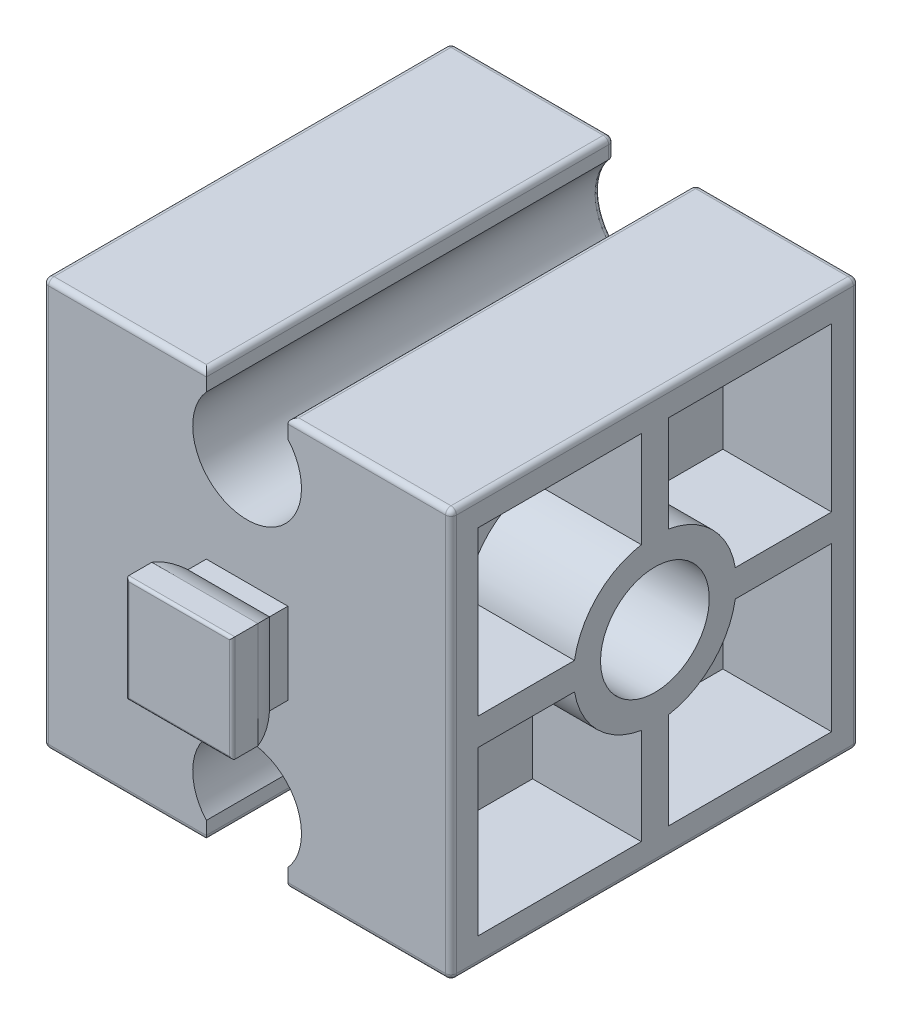
SolidWorks part; units mm, degrees
note: The reader was unsure of these and kept them because the rebuilt part matched: shared geometry of "草图6<2>".
ref_plane "前视基准面" through (0, 0, 0) normal (0, 0, 1) x (1, 0, 0)
ref_plane "上视基准面" through (0, 0, 0) normal (0, 1, 0) x (1, 0, 0)
ref_plane "右视基准面" through (0, 0, 0) normal (1, 0, 0) x (0, 0, -1)
sketch "草图1" plane through (0, 0, 0) normal (0, 0, 1) x (1, 0, 0)
  line L1 (-7.5, -7.5) -> (7.5, -7.5)
  line L2 (-7.5, -7.5) -> (-7.5, 7.5)
  line L3 (-7.5, 7.5) -> (7.5, 7.5)
  line L4 (7.5, -7.5) -> (7.5, 7.5)
extrude "凸台-拉伸1" add sketch "草图1" against normal blind 15
sketch "草图2" plane through (0, 0, 0) normal (0, 0, 1) x (1, 0, 0)
  line L1 (-1.5, -1.5) -> (1.5, -1.5)
  line L2 (-1.5, -1.5) -> (-1.5, 1.5)
  line L3 (-1.5, 1.5) -> (1.5, 1.5)
  line L4 (1.5, -1.5) -> (1.5, 1.5)
extrude "凸台-拉伸2" add sketch "草图2" along normal blind 1
sketch "草图3" plane through (0, 0, 0) normal (1, 0, 0) x (0, 0, -1)
  line L0 (-2.5, 1.95) -> (-2.5, -1.95)
  line L1 (-2.5, 1.95) -> (-1.5556, 1.95)
  line L2 (-2.5, -1.95) -> (-1.5556, -1.95)
  line L3 (-0.6771, 1.5) -> (-0.6771, -1.5)
  arc A0 (-1.5556, -1.95) -> (-0.6771, -1.5) centre (-2, 0) ccw
  arc A1 (-0.6771, 1.5) -> (-1.5556, 1.95) centre (-2, 0) ccw
extrude "凸台-拉伸3" add sketch "草图3" along normal blind 4 and the other way blind 4 separate body
sketch "草图4" plane through (0, 0, 0) normal (0, 1, 0) x (1, 0, 0)
  line L0 (-4, -2.5) -> (-1.95, -2.5)
  line L1 (-1.95, -2.5) -> (-1.95, -1.5556)
  line L2 (1.95, -2.5) -> (1.95, -1.5556)
  line L3 (-4, -2.5) -> (-4, -0.6771)
  line L4 (-1.5, -0.6771) -> (-4, -0.6771)
  line L5 (4, -0.6771) -> (4, -2.5)
  line L7 (1.95, -2.5) -> (4, -2.5)
  line L8 (-4, -0.6771) -> (4, -0.6771) construction
  line L12 (1.5, -0.6771) -> (4, -0.6771)
  arc A0 (-1.5, -0.6771) -> (-1.95, -1.5556) centre (0, -2) ccw
  arc A1 (1.95, -1.5556) -> (1.5, -0.6771) centre (0, -2) ccw
extrude "切除-拉伸1" cut sketch "草图4" against normal up to next (1.95 mm away) and the other way up to next (1.95 mm away)
sketch "草图5" plane through (-7.5, 0, 0) normal (-1, 0, 0) x (0, 0, 1)
  circle A0 centre (-7.5, 0) radius 2
extrude "切除-拉伸2" cut sketch "草图5" against normal through all
sketch "草图6" plane through (-7.5, 0, 0) normal (-1, 0, 0) x (0, 0, 1)
  line L0 (-8, 6.5) -> (-8, 2.958)
  line L1 (-14, -6.5) -> (-8, -6.5)
  line L2 (-14, -6.5) -> (-14, -0.5)
  line L3 (-14, 6.5) -> (-8, 6.5)
  line L4 (-1, -6.5) -> (-1, -0.5)
  line L5 (-7, 6.5) -> (-7, 2.958)
  line L6 (-14, 0.5) -> (-10.458, 0.5)
  line L7 (-14, -0.5) -> (-10.458, -0.5)
  line L8 (-8, -2.958) -> (-8, -6.5)
  line L9 (-4.542, 0.5) -> (-1, 0.5)
  line L10 (-4.542, -0.5) -> (-1, -0.5)
  line L11 (-7, -2.958) -> (-7, -6.5)
  line L12 (-7, 6.5) -> (-1, 6.5)
  line L13 (-14, 0.5) -> (-14, 6.5)
  line L14 (-7, -6.5) -> (-1, -6.5)
  line L15 (-1, 0.5) -> (-1, 6.5)
  arc A0 (-7, -2.958) -> (-4.542, -0.5) centre (-7.5, 0) ccw
  arc A1 (-10.458, -0.5) -> (-8, -2.958) centre (-7.5, 0) ccw
  arc A2 (-8, 2.958) -> (-10.458, 0.5) centre (-7.5, 0) ccw
  arc A3 (-4.542, 0.5) -> (-7, 2.958) centre (-7.5, 0) ccw
extrude "切除-拉伸3" cut sketch "草图6" against normal blind 4
extrude "切除-拉伸4" cut sketch "草图6<2>" against normal up to next from offset 11
sketch "草图6<2>" plane through (-7.5, 0, 0) normal (-1, 0, 0) x (0, 0, 1) same geometry as "草图6"
sketch "草图7" plane through (0, 0, 0) normal (0, 0, 1) x (1, 0, 0)
  line L0 (-1.5, -7.5) -> (-1.5, -6.8229)
  line L1 (-7.5, -7.5) -> (7.5, -7.5) construction
  line L2 (1.5, -7.5) -> (1.5, -6.8229)
  line L3 (-1.5, 7.5) -> (1.5, 7.5)
  line L5 (1.5, 7.5) -> (1.5, 6.8229)
  line L6 (-1.5, 7.5) -> (-1.5, 6.8229)
  line L7 (-1.5, -7.5) -> (1.5, -7.5)
  arc A0 (1.5, -6.8229) -> (-1.5, -6.8229) centre (0, -5.5) ccw
  arc A1 (-1.5, 6.8229) -> (1.5, 6.8229) centre (0, 5.5) ccw
extrude "切除-拉伸5" cut sketch "草图7" against normal through all
fillet "圆角1" radius 0.1 4 edges at (1.95, 0, 2.5) (0, -1.95, 2.5) (-1.95, 0, 2.5) (0, 1.95, 2.5)
fillet "圆角2" radius 0.2 26 edges at (0, -3.5, -15) (1.5, -7.1614, -15) (4.5, -7.5, -15) (7.5, 0, -15) (4.5, 7.5, -15) (1.5, 7.1614, -15) (0, 3.5, -15) (-1.5, 7.1614, -15) (-4.5, 7.5, -15) (-7.5, 0, -15) (-4.5, -7.5, -15) (-1.5, -7.1614, -15) (-7.5, 0, 0) (-4.5, 7.5, 0) (4.5, 7.5, 0) (7.5, 0, 0) (4.5, -7.5, 0) (-4.5, -7.5, 0) (7.5, 7.5, -7.5) (1.5, 7.5, -7.5) (-7.5, 7.5, -7.5) (-1.5, 7.5, -7.5) (7.5, -7.5, -7.5) (1.5, -7.5, -7.5) (-7.5, -7.5, -7.5) (-1.5, -7.5, -7.5)
ref_plane "基准面1" through (0, 0, -7.5) normal (0, 0, 1) x (1, 0, 0)
mirror "镜向2" about plane through (0, 0, -7.5) normal (0, 0, 1) of "凸台-拉伸3", "切除-拉伸1", "圆角1", "凸台-拉伸2"
